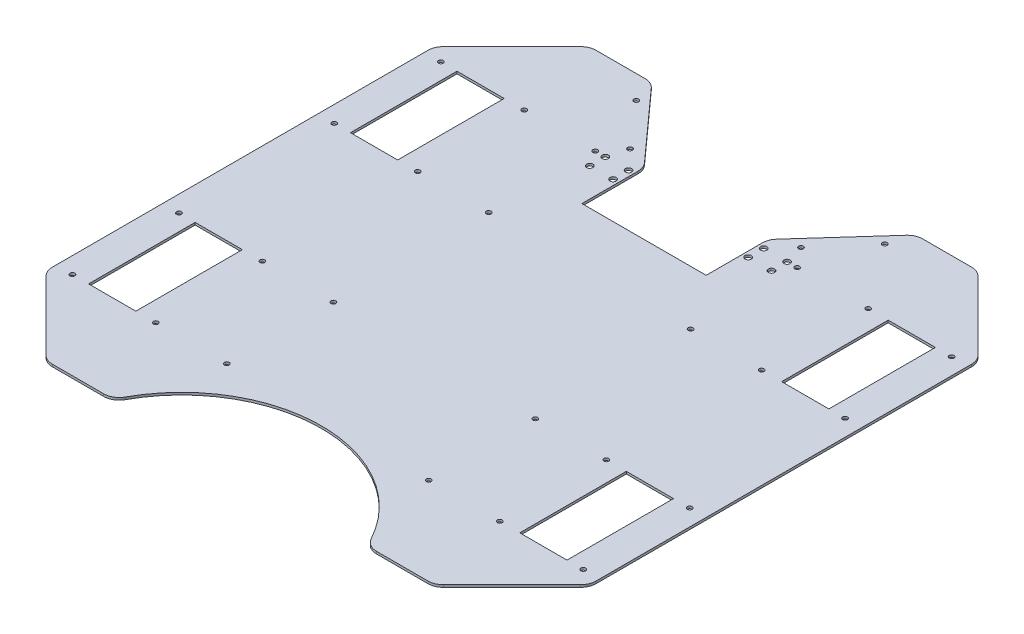
SolidWorks part; units mm, degrees
material "PMMA"
ref_plane "前视基准面" through (0, 0, 0) normal (0, 0, 1) x (1, 0, 0)
ref_plane "上视基准面" through (0, 0, 0) normal (0, 1, 0) x (1, 0, 0)
ref_plane "右视基准面" through (0, 0, 0) normal (1, 0, 0) x (0, 0, -1)
other "Configuration Table"
sketch "草图1" plane through (0, 0, 0) normal (0, 1, 0) x (1, 0, 0)
  line L0 (-125, 175) -> (-175, 125)
  line L1 (125, -175) -> (81.7103, -175)
  line L2 (175, -125) -> (175, 125)
  line L3 (125, 175) -> (85, 175)
  line L4 (-175, -125) -> (-175, 125)
  line L5 (-85, 175) -> (-40, 125)
  line L7 (125, 175) -> (175, 125)
  line L8 (175, -125) -> (125, -175)
  line L9 (-125, -175) -> (-175, -125)
  line L10 (40, 125) -> (85, 175)
  line L11 (-85, 175) -> (-125, 175)
  line L12 (40, 125) -> (40, 85)
  line L13 (40, 85) -> (-40, 85)
  line L14 (-40, 85) -> (-40, 125)
  line L15 (-153.994, 50) -> (-123.594, 50)
  line L16 (-123.594, 50) -> (-123.594, 118.58)
  line L17 (-123.594, 118.58) -> (-153.994, 118.58)
  line L18 (-153.994, 118.58) -> (-153.994, 50)
  line L19 (123.594, 50) -> (153.994, 50)
  line L20 (153.994, 50) -> (153.994, 118.58)
  line L21 (153.994, 118.58) -> (123.594, 118.58)
  line L22 (123.594, 118.58) -> (123.594, 50)
  line L23 (-175, 0) -> (175, 0) construction
  line L24 (-123.594, -118.58) -> (-153.994, -118.58)
  line L25 (-123.594, -50) -> (-123.594, -118.58)
  line L26 (-153.994, -50) -> (-123.594, -50)
  line L27 (-153.994, -118.58) -> (-153.994, -50)
  line L28 (153.994, -118.58) -> (123.594, -118.58)
  line L29 (153.994, -50) -> (153.994, -118.58)
  line L30 (123.594, -50) -> (153.994, -50)
  line L31 (123.594, -118.58) -> (123.594, -50)
  line L32 (-81.7103, -175) -> (-125, -175)
  line L33 (-80, 160) -> (-55, 131) construction
  line L34 (0, 0) -> (0, 46.7243)
  circle A0 centre (-55, 131) radius 1.55
  circle A1 centre (-80, 160) radius 1.55
  circle A2 centre (55, 131) radius 1.55
  circle A3 centre (80, 160) radius 1.55
  circle A4 centre (-65, 118.58) radius 1.55
  circle A5 centre (-65, 50) radius 1.55
  circle A6 centre (-110.72, 50) radius 1.55
  circle A7 centre (-110.72, 118.58) radius 1.55
  circle A12 centre (-164.434, 118.58) radius 1.55
  circle A13 centre (-164.434, 50) radius 1.55
  circle A14 centre (-65, -118.58) radius 1.55
  circle A15 centre (-65, -50) radius 1.55
  circle A16 centre (-110.72, -50) radius 1.55
  circle A17 centre (-110.72, -118.58) radius 1.55
  circle A18 centre (-164.434, -50) radius 1.55
  circle A19 centre (-164.434, -118.58) radius 1.55
  circle A20 centre (65, 50) radius 1.55
  circle A21 centre (110.72, 50) radius 1.55
  circle A22 centre (110.72, 118.58) radius 1.55
  circle A23 centre (65, 118.58) radius 1.55
  circle A24 centre (164.434, 118.58) radius 1.55
  circle A25 centre (164.434, 50) radius 1.55
  circle A26 centre (164.434, -118.58) radius 1.55
  circle A27 centre (164.434, -50) radius 1.55
  circle A28 centre (110.72, -50) radius 1.55
  circle A29 centre (110.72, -118.58) radius 1.55
  circle A30 centre (65, -118.58) radius 1.55
  circle A31 centre (65, -50) radius 1.55
  arc A32 (-81.7103, -175) -> (81.7103, -175) centre (0, -212.7283) cw
  circle A33 centre (-58.5, 118.58) radius 2
  circle A34 centre (-43.5, 118.58) radius 2
  circle A35 centre (-58.5, 108.58) radius 2
  circle A36 centre (-43.5, 108.58) radius 2
  circle A37 centre (43.5, 108.58) radius 2
  circle A38 centre (58.5, 108.58) radius 2
  circle A39 centre (43.5, 118.58) radius 2
  circle A40 centre (58.5, 118.58) radius 2
  point P0 (0, 0)
  point P1 (-85, 175)
  point P2 (85, 175)
  point P3 (40, 125)
  point P4 (-40, 125)
  point P6 (125, 175)
  point P8 (175, 125)
  point P10 (175, -125)
  point P11 (125, -175)
  point P12 (-125, -175)
  point P13 (-175, -125)
  point P24 (-80, 160)
  point P25 (-55, 131)
  point P26 (55, 131)
  point P27 (80, 160)
  point P36 (-164.434, 118.58)
  point P37 (-164.434, 50)
  point P38 (-153.994, 118.58)
  point P39 (-123.594, 50)
  point P40 (-110.72, 118.58)
  point P41 (-110.72, 50)
  point P42 (-65, 118.58)
  point P43 (-65, 50)
  point P47 (-123.594, 118.58)
  point P53 (-153.994, 50)
  point P66 (-40, 85)
  point P67 (40, 85)
  point P70 (110.72, 50)
  point P71 (65, 50)
  point P72 (123.594, 50)
  point P73 (153.994, 50)
  point P74 (164.434, 50)
  point P75 (65, 118.58)
  point P76 (110.72, 118.58)
  point P77 (123.594, 118.58)
  point P78 (153.994, 118.58)
  point P81 (164.434, 118.58)
  point P85 (-65, -118.58)
  point P88 (-65, -50)
  point P91 (-110.72, -50)
  point P94 (-110.72, -118.58)
  point P101 (-164.434, -50)
  point P104 (-164.434, -118.58)
  point P118 (164.434, -118.58)
  point P121 (164.434, -50)
  point P128 (110.72, -50)
  point P131 (110.72, -118.58)
  point P134 (65, -118.58)
  point P137 (65, -50)
  dimension "D29" = 3.1
  dimension "D30" = 3.1
  dimension "D31" = 3.1
  dimension "D32" = 3.1
  dimension "D40" = 3.1
  dimension "D41" = 3.1
  dimension "D42" = 3.1
  dimension "D43" = 3.1
  dimension "D44" = 3.1
  dimension "D45" = 3.1
  dimension "D46" = 3.1
  dimension "D47" = 3.1
  dimension "D48" = 3.1
  dimension "D49" = 3.1
  dimension "D60" = 3.1
  dimension "D61" = 3.1
  dimension "D62" = 43.2897
  dimension "D63" = 90
  dimension "D66" = 3.5
  dimension "D68" = 10
  dimension "D1" = 175
  dimension "D2" = 175
  dimension "D3" = 125
  dimension "D4" = 125
  dimension "D5" = 125
  dimension "D6" = 125
  dimension "D7" = 125
  dimension "D8" = 125
  dimension "D9" = 125
  dimension "D10" = 125
  dimension "D11" = 175
  dimension "D12" = 175
  dimension "D13" = 40
  dimension "D14" = 40
  dimension "D15" = 85
  dimension "D16" = 85
  dimension "D17" = 125
  dimension "D18" = 125
  dimension "D19" = 40
  dimension "D20" = 45
  dimension "D21" = 160
  dimension "D22" = 160
  dimension "D23" = 80
  dimension "D24" = 80
  dimension "D25" = 55
  dimension "D26" = 131
  dimension "D27" = 55
  dimension "D28" = 131
  dimension "D33" = 50
  dimension "D34" = 118.58
  dimension "D35" = 65
  dimension "D36" = 45.72
  dimension "D37" = 12.874
  dimension "D38" = 30.4
  dimension "D39" = 10.44
  dimension "D50" = 40
  dimension "D51" = 40
  dimension "D52" = 85
  dimension "D53" = 85
  dimension "D54" = 138.013
  dimension "D55" = 65
  dimension "D56" = 45.72
  dimension "D57" = 12.874
  dimension "D58" = 30.4
  dimension "D59" = 10.44
  dimension "D64" = 0
  dimension "D65" = 25
  dimension "D67" = 15
extrude "凸台-拉伸1" add sketch "草图1" along normal blind 1.5 contours A1 | A0 | L8 L1 A32 L32 L9 L4 L0 L11 L5 L14 L13 L12 L10 L3 L7 L2 | A5 | A3 | A2 | A4 | A7 | A12 | L16 L17 L18 L15 | A6 | L21 L22 L19 L20 | A13 | A16 | A17 | A14 | A15 | A18 | A19 | L25 L24 L27 L26 | A20 | A21 | A22 | A23 | A24 | A25 | A28 | A26 | A27 | L28 L31 L30 L29 | A30 | A31 | A29
fillet "圆角1" radius 10 1 edges at (-40, 0.75, -125)
fillet "圆角2" radius 10 1 edges at (40, 0.75, -125)
fillet "圆角3" radius 10 12 edges at (-85, 0.75, -175) (85, 0.75, -175) (125, 0.75, -175) (175, 0.75, -125) (175, 0.75, 125) (125, 0.75, 175) (81.7103, 0.75, 175) (-81.7103, 0.75, 175) (-125, 0.75, 175) (-175, 0.75, 125) (-175, 0.75, -125) (-125, 0.75, -175)
extrude "切除-拉伸3" cut sketch "草图1<5>" along normal blind 10 contours A40 | A39 | A38 | A37 | A36 | A33 | A35 | A34 region at (-58.5, 0, -118.58) region at (-58.5, 0, -108.58) region at (-43.5, 0, -108.58) region at (43.5, 0, -108.58) region at (58.5, 0, -108.58) region at (43.5, 0, -118.58) region at (58.5, 0, -118.58)
sketch "草图1<5>" plane through (0, 0, 0) normal (0, 1, 0) x (1, 0, 0) same geometry as "草图1"
